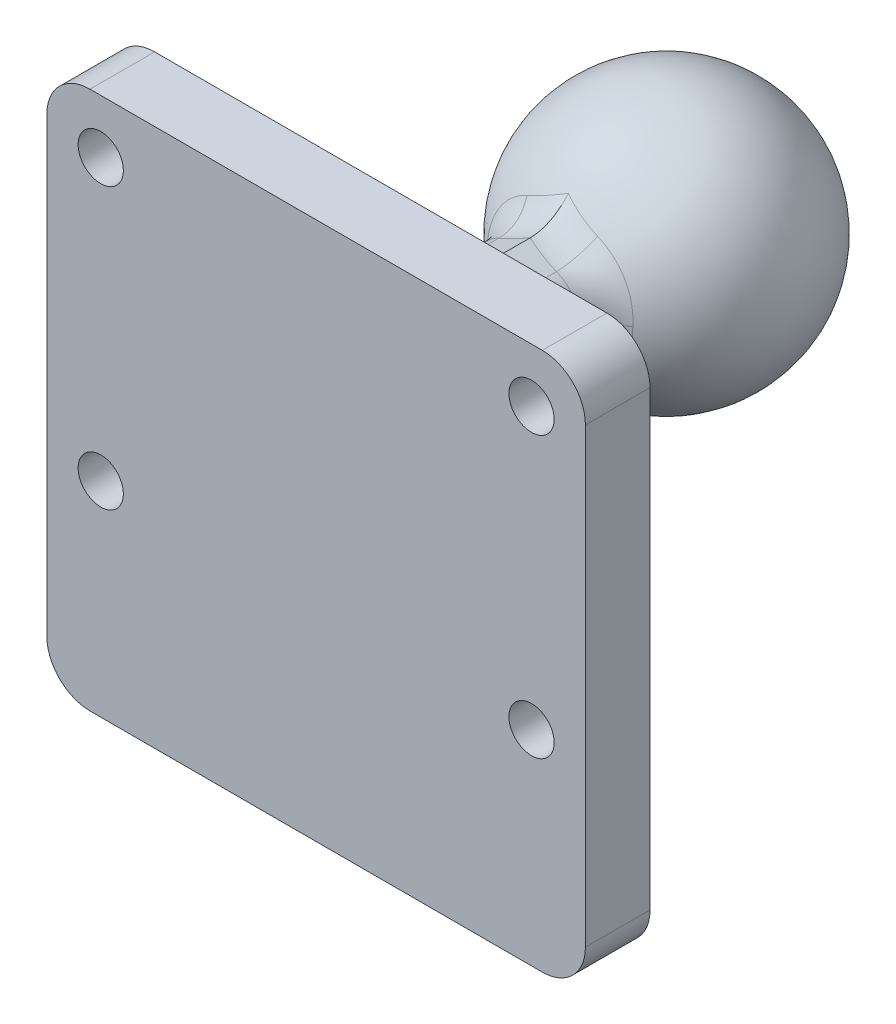
SolidWorks part; units mm, degrees
material "ABS"
ref_plane "Front Plane" through (0, 0, 0) normal (0, 0, 1) x (1, 0, 0)
ref_plane "Top Plane" through (0, 0, 0) normal (0, 1, 0) x (1, 0, 0)
ref_plane "Right Plane" through (0, 0, 0) normal (1, 0, 0) x (0, 0, -1)
sketch "Sketch1" plane through (0, 0, 0) normal (0, 0, 1) x (1, 0, 0)
  line L1 (-12.5, 12.5) -> (12.5, 12.5)
  line L2 (-12.5, 12.5) -> (-12.5, -12.5)
  line L3 (-12.5, -12.5) -> (12.5, -12.5)
  line L4 (12.5, 12.5) -> (12.5, -12.5)
  line L5 (-12.5, 12.5) -> (12.5, -12.5) construction
  line L6 (-12.5, -12.5) -> (12.5, 12.5) construction
  point P0 (0, 0)
  dimension "D1" = 25
  dimension "D2" = 25
extrude "Boss-Extrude1" add sketch "Sketch1" along normal blind 3
sketch "Sketch2" plane through (0, 0, 3) normal (0, 0, 1) x (1, 0, 0)
  line L0 (-12.5, 12.5) -> (-12.5, -12.5) construction
  line L1 (12.5, 12.5) -> (-12.5, 12.5) construction
  circle A0 centre (-10, 10) radius 1.05
  dimension "D1" = 2.1
  dimension "D2" = 2.5
  dimension "D3" = 2.5
extrude "Cut-Extrude1" cut sketch "Sketch2" against normal through all
pattern_linear "LPattern1" count 2 spacing 20 along (1, 0, 0) count 2 spacing 13 along (0, -1, 0) of "Cut-Extrude1"
sketch "Sketch3" plane through (0, 0, 0) normal (1, 0, 0) x (0, 0, -1)
  line L0 (-2.6514, 6.8046) -> (-3, -5.317)
  line L2 (-3, -5.317) -> (14.2961, 0.9859)
  line L3 (-2.6514, 6.8046) -> (13.2689, 6.8046)
  line L4 (-3, -12.5) -> (-3, 12.5) construction
  arc A0 (14.2961, 0.9859) -> (13.2689, 6.8046) centre (13.2689, 3.8046) ccw
  point P2 (-3, -7.1835)
  point P8 (-2.8161, 7.7937)
  point P9 (-2.6219, 5.0055)
  point P10 (-3, -5.317)
  point P11 (-2.6514, 6.8046)
  dimension "D1" = 3
  dimension "D2" = 16
extrude "Boss-Extrude2" add sketch "Sketch3" along normal mid plane 5 draft 25
ref_axis "Axis1" through (0, -7.8726, -13.2689) along (0, 1, 0)
sketch "Sketch4" plane through (0, 0, 0) normal (1, 0, 0) x (0, 0, -1)
  line L0 (13.2689, -7.8726) -> (13.2689, 15.8931) construction
  line L1 (13.2689, 9.8046) -> (13.2689, -2.1954)
  arc A0 (13.2689, 9.8046) -> (13.2689, -2.1954) centre (13.2689, 3.8046) cw
  dimension "D1" = 6
revolve "Revolve1" add sketch "Sketch4" angle 360 about axis through (0, -7.8726, -13.2689) along (0, 1, 0)
fillet "Fillet1" radius 2 20 edges at (-1.25, 6.2217, 0) (1.25, -3.6034, 0) (1.2535, -0.2958, -9.0718) (1.2535, 6.2201, -7.9216) (2.5, -1.3303, -4.5354) (2.5, 1.3279, 0) (2.5, 5.6388, -4.0661) (2.5, 2.8564, -7.8976) (-2.5, 1.3279, 0) (-2.5, -1.3303, -4.5354) (-2.5, 2.8564, -7.8976) (-2.5, 5.6388, -4.0661) (-1.2535, -0.2958, -9.0718) (-1.25, -3.6034, 0) (1.25, 6.2217, 0) (-1.2535, 6.2201, -7.9216) (-12.5, -12.5, 1.5) (12.5, -12.5, 1.5) (-12.5, 12.5, 1.5) (12.5, 12.5, 1.5)
